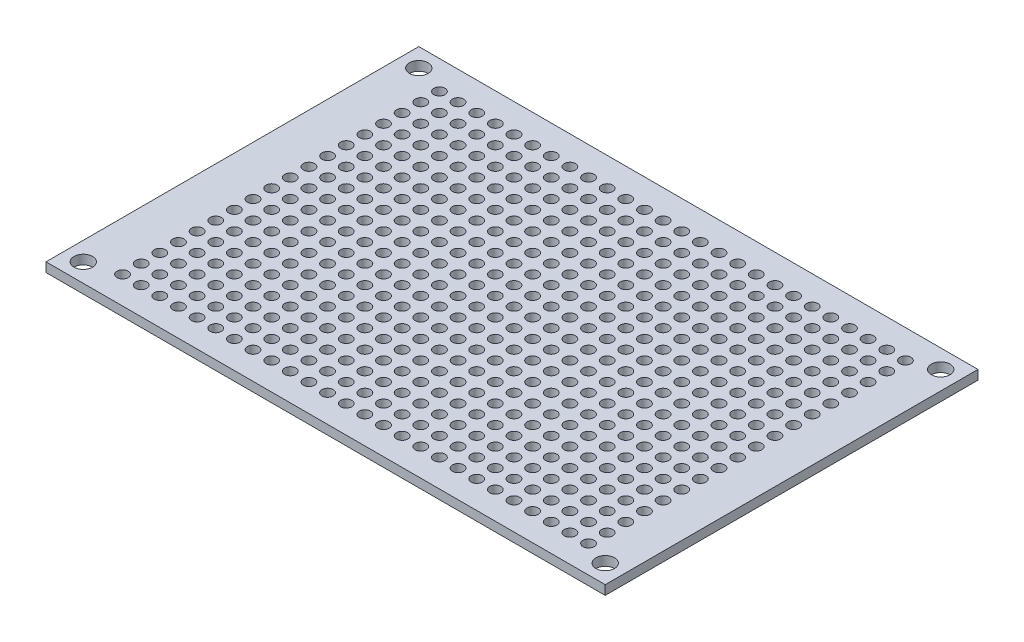
SolidWorks part; units mm, degrees
ref_plane "Front Plane" through (0, 0, 0) normal (0, 0, 1) x (1, 0, 0)
ref_plane "Top Plane" through (0, 0, 0) normal (0, 1, 0) x (1, 0, 0)
ref_plane "Right Plane" through (0, 0, 0) normal (1, 0, 0) x (0, 0, -1)
sketch "Sketch1" plane through (0, 0, 0) normal (0, 1, 0) x (1, 0, 0)
  line L1 (-30, -20) -> (30, -20)
  line L2 (-30, -20) -> (-30, 20)
  line L3 (-30, 20) -> (30, 20)
  line L4 (30, -20) -> (30, 20)
  line L5 (-30, -20) -> (30, 20) construction
  line L6 (-30, 20) -> (30, -20) construction
  circle A0 centre (-28, 18) radius 1
  circle A1 centre (28, 18) radius 1
  circle A2 centre (28, -18) radius 1
  circle A3 centre (-28, -18) radius 1
  circle A4 centre (-24.7248, 16.9363) radius 0.6
  circle A5 centre (-22.7248, 16.9363) radius 0.6
  circle A6 centre (-20.7248, 16.9363) radius 0.6
  circle A7 centre (-18.7248, 16.9363) radius 0.6
  circle A8 centre (-16.7248, 16.9363) radius 0.6
  circle A9 centre (-14.7248, 16.9363) radius 0.6
  circle A10 centre (-12.7248, 16.9363) radius 0.6
  circle A11 centre (-10.7248, 16.9363) radius 0.6
  circle A12 centre (-8.7248, 16.9363) radius 0.6
  circle A13 centre (-6.7248, 16.9363) radius 0.6
  circle A14 centre (-4.7248, 16.9363) radius 0.6
  circle A15 centre (-2.7248, 16.9363) radius 0.6
  circle A16 centre (-0.7248, 16.9363) radius 0.6
  circle A17 centre (1.2752, 16.9363) radius 0.6
  circle A18 centre (3.2752, 16.9363) radius 0.6
  circle A19 centre (5.2752, 16.9363) radius 0.6
  circle A20 centre (7.2752, 16.9363) radius 0.6
  circle A21 centre (9.2752, 16.9363) radius 0.6
  circle A22 centre (11.2752, 16.9363) radius 0.6
  circle A23 centre (13.2752, 16.9363) radius 0.6
  circle A24 centre (15.2752, 16.9363) radius 0.6
  circle A25 centre (17.2752, 16.9363) radius 0.6
  circle A26 centre (19.2752, 16.9363) radius 0.6
  circle A27 centre (21.2752, 16.9363) radius 0.6
  circle A28 centre (23.2752, 16.9363) radius 0.6
  circle A29 centre (25.2752, 16.9363) radius 0.6
  circle A30 centre (-22.7248, 14.9363) radius 0.6
  circle A31 centre (-20.7248, 14.9363) radius 0.6
  circle A32 centre (-18.7248, 14.9363) radius 0.6
  circle A33 centre (-16.7248, 14.9363) radius 0.6
  circle A34 centre (-14.7248, 14.9363) radius 0.6
  circle A35 centre (-12.7248, 14.9363) radius 0.6
  circle A36 centre (-10.7248, 14.9363) radius 0.6
  circle A37 centre (-8.7248, 14.9363) radius 0.6
  circle A38 centre (-6.7248, 14.9363) radius 0.6
  circle A39 centre (-4.7248, 14.9363) radius 0.6
  circle A40 centre (-2.7248, 14.9363) radius 0.6
  circle A41 centre (-0.7248, 14.9363) radius 0.6
  circle A42 centre (1.2752, 14.9363) radius 0.6
  circle A43 centre (3.2752, 14.9363) radius 0.6
  circle A44 centre (5.2752, 14.9363) radius 0.6
  circle A45 centre (7.2752, 14.9363) radius 0.6
  circle A46 centre (9.2752, 14.9363) radius 0.6
  circle A47 centre (11.2752, 14.9363) radius 0.6
  circle A48 centre (13.2752, 14.9363) radius 0.6
  circle A49 centre (15.2752, 14.9363) radius 0.6
  circle A50 centre (17.2752, 14.9363) radius 0.6
  circle A51 centre (19.2752, 14.9363) radius 0.6
  circle A52 centre (21.2752, 14.9363) radius 0.6
  circle A53 centre (23.2752, 14.9363) radius 0.6
  circle A54 centre (25.2752, 14.9363) radius 0.6
  circle A55 centre (-22.7248, 12.9363) radius 0.6
  circle A56 centre (-20.7248, 12.9363) radius 0.6
  circle A57 centre (-18.7248, 12.9363) radius 0.6
  circle A58 centre (-16.7248, 12.9363) radius 0.6
  circle A59 centre (-14.7248, 12.9363) radius 0.6
  circle A60 centre (-12.7248, 12.9363) radius 0.6
  circle A61 centre (-10.7248, 12.9363) radius 0.6
  circle A62 centre (-8.7248, 12.9363) radius 0.6
  circle A63 centre (-6.7248, 12.9363) radius 0.6
  circle A64 centre (-4.7248, 12.9363) radius 0.6
  circle A65 centre (-2.7248, 12.9363) radius 0.6
  circle A66 centre (-0.7248, 12.9363) radius 0.6
  circle A67 centre (1.2752, 12.9363) radius 0.6
  circle A68 centre (3.2752, 12.9363) radius 0.6
  circle A69 centre (5.2752, 12.9363) radius 0.6
  circle A70 centre (7.2752, 12.9363) radius 0.6
  circle A71 centre (9.2752, 12.9363) radius 0.6
  circle A72 centre (11.2752, 12.9363) radius 0.6
  circle A73 centre (13.2752, 12.9363) radius 0.6
  circle A74 centre (15.2752, 12.9363) radius 0.6
  circle A75 centre (17.2752, 12.9363) radius 0.6
  circle A76 centre (19.2752, 12.9363) radius 0.6
  circle A77 centre (21.2752, 12.9363) radius 0.6
  circle A78 centre (23.2752, 12.9363) radius 0.6
  circle A79 centre (25.2752, 12.9363) radius 0.6
  circle A80 centre (-22.7248, 10.9363) radius 0.6
  circle A81 centre (-20.7248, 10.9363) radius 0.6
  circle A82 centre (-18.7248, 10.9363) radius 0.6
  circle A83 centre (-16.7248, 10.9363) radius 0.6
  circle A84 centre (-14.7248, 10.9363) radius 0.6
  circle A85 centre (-12.7248, 10.9363) radius 0.6
  circle A86 centre (-10.7248, 10.9363) radius 0.6
  circle A87 centre (-8.7248, 10.9363) radius 0.6
  circle A88 centre (-6.7248, 10.9363) radius 0.6
  circle A89 centre (-4.7248, 10.9363) radius 0.6
  circle A90 centre (-2.7248, 10.9363) radius 0.6
  circle A91 centre (-0.7248, 10.9363) radius 0.6
  circle A92 centre (1.2752, 10.9363) radius 0.6
  circle A93 centre (3.2752, 10.9363) radius 0.6
  circle A94 centre (5.2752, 10.9363) radius 0.6
  circle A95 centre (7.2752, 10.9363) radius 0.6
  circle A96 centre (9.2752, 10.9363) radius 0.6
  circle A97 centre (11.2752, 10.9363) radius 0.6
  circle A98 centre (13.2752, 10.9363) radius 0.6
  circle A99 centre (15.2752, 10.9363) radius 0.6
  circle A100 centre (17.2752, 10.9363) radius 0.6
  circle A101 centre (19.2752, 10.9363) radius 0.6
  circle A102 centre (21.2752, 10.9363) radius 0.6
  circle A103 centre (23.2752, 10.9363) radius 0.6
  circle A104 centre (25.2752, 10.9363) radius 0.6
  circle A105 centre (-22.7248, 8.9363) radius 0.6
  circle A106 centre (-20.7248, 8.9363) radius 0.6
  circle A107 centre (-18.7248, 8.9363) radius 0.6
  circle A108 centre (-16.7248, 8.9363) radius 0.6
  circle A109 centre (-14.7248, 8.9363) radius 0.6
  circle A110 centre (-12.7248, 8.9363) radius 0.6
  circle A111 centre (-10.7248, 8.9363) radius 0.6
  circle A112 centre (-8.7248, 8.9363) radius 0.6
  circle A113 centre (-6.7248, 8.9363) radius 0.6
  circle A114 centre (-4.7248, 8.9363) radius 0.6
  circle A115 centre (-2.7248, 8.9363) radius 0.6
  circle A116 centre (-0.7248, 8.9363) radius 0.6
  circle A117 centre (1.2752, 8.9363) radius 0.6
  circle A118 centre (3.2752, 8.9363) radius 0.6
  circle A119 centre (5.2752, 8.9363) radius 0.6
  circle A120 centre (7.2752, 8.9363) radius 0.6
  circle A121 centre (9.2752, 8.9363) radius 0.6
  circle A122 centre (11.2752, 8.9363) radius 0.6
  circle A123 centre (13.2752, 8.9363) radius 0.6
  circle A124 centre (15.2752, 8.9363) radius 0.6
  circle A125 centre (17.2752, 8.9363) radius 0.6
  circle A126 centre (19.2752, 8.9363) radius 0.6
  circle A127 centre (21.2752, 8.9363) radius 0.6
  circle A128 centre (23.2752, 8.9363) radius 0.6
  circle A129 centre (25.2752, 8.9363) radius 0.6
  circle A130 centre (-22.7248, 6.9363) radius 0.6
  circle A131 centre (-20.7248, 6.9363) radius 0.6
  circle A132 centre (-18.7248, 6.9363) radius 0.6
  circle A133 centre (-16.7248, 6.9363) radius 0.6
  circle A134 centre (-14.7248, 6.9363) radius 0.6
  circle A135 centre (-12.7248, 6.9363) radius 0.6
  circle A136 centre (-10.7248, 6.9363) radius 0.6
  circle A137 centre (-8.7248, 6.9363) radius 0.6
  circle A138 centre (-6.7248, 6.9363) radius 0.6
  circle A139 centre (-4.7248, 6.9363) radius 0.6
  circle A140 centre (-2.7248, 6.9363) radius 0.6
  circle A141 centre (-0.7248, 6.9363) radius 0.6
  circle A142 centre (1.2752, 6.9363) radius 0.6
  circle A143 centre (3.2752, 6.9363) radius 0.6
  circle A144 centre (5.2752, 6.9363) radius 0.6
  circle A145 centre (7.2752, 6.9363) radius 0.6
  circle A146 centre (9.2752, 6.9363) radius 0.6
  circle A147 centre (11.2752, 6.9363) radius 0.6
  circle A148 centre (13.2752, 6.9363) radius 0.6
  circle A149 centre (15.2752, 6.9363) radius 0.6
  circle A150 centre (17.2752, 6.9363) radius 0.6
  circle A151 centre (19.2752, 6.9363) radius 0.6
  circle A152 centre (21.2752, 6.9363) radius 0.6
  circle A153 centre (23.2752, 6.9363) radius 0.6
  circle A154 centre (25.2752, 6.9363) radius 0.6
  circle A155 centre (-22.7248, 4.9363) radius 0.6
  circle A156 centre (-20.7248, 4.9363) radius 0.6
  circle A157 centre (-18.7248, 4.9363) radius 0.6
  circle A158 centre (-16.7248, 4.9363) radius 0.6
  circle A159 centre (-14.7248, 4.9363) radius 0.6
  circle A160 centre (-12.7248, 4.9363) radius 0.6
  circle A161 centre (-10.7248, 4.9363) radius 0.6
  circle A162 centre (-8.7248, 4.9363) radius 0.6
  circle A163 centre (-6.7248, 4.9363) radius 0.6
  circle A164 centre (-4.7248, 4.9363) radius 0.6
  circle A165 centre (-2.7248, 4.9363) radius 0.6
  circle A166 centre (-0.7248, 4.9363) radius 0.6
  circle A167 centre (1.2752, 4.9363) radius 0.6
  circle A168 centre (3.2752, 4.9363) radius 0.6
  circle A169 centre (5.2752, 4.9363) radius 0.6
  circle A170 centre (7.2752, 4.9363) radius 0.6
  circle A171 centre (9.2752, 4.9363) radius 0.6
  circle A172 centre (11.2752, 4.9363) radius 0.6
  circle A173 centre (13.2752, 4.9363) radius 0.6
  circle A174 centre (15.2752, 4.9363) radius 0.6
  circle A175 centre (17.2752, 4.9363) radius 0.6
  circle A176 centre (19.2752, 4.9363) radius 0.6
  circle A177 centre (21.2752, 4.9363) radius 0.6
  circle A178 centre (23.2752, 4.9363) radius 0.6
  circle A179 centre (25.2752, 4.9363) radius 0.6
  circle A180 centre (-22.7248, 2.9363) radius 0.6
  circle A181 centre (-20.7248, 2.9363) radius 0.6
  circle A182 centre (-18.7248, 2.9363) radius 0.6
  circle A183 centre (-16.7248, 2.9363) radius 0.6
  circle A184 centre (-14.7248, 2.9363) radius 0.6
  circle A185 centre (-12.7248, 2.9363) radius 0.6
  circle A186 centre (-10.7248, 2.9363) radius 0.6
  circle A187 centre (-8.7248, 2.9363) radius 0.6
  circle A188 centre (-6.7248, 2.9363) radius 0.6
  circle A189 centre (-4.7248, 2.9363) radius 0.6
  circle A190 centre (-2.7248, 2.9363) radius 0.6
  circle A191 centre (-0.7248, 2.9363) radius 0.6
  circle A192 centre (1.2752, 2.9363) radius 0.6
  circle A193 centre (3.2752, 2.9363) radius 0.6
  circle A194 centre (5.2752, 2.9363) radius 0.6
  circle A195 centre (7.2752, 2.9363) radius 0.6
  circle A196 centre (9.2752, 2.9363) radius 0.6
  circle A197 centre (11.2752, 2.9363) radius 0.6
  circle A198 centre (13.2752, 2.9363) radius 0.6
  circle A199 centre (15.2752, 2.9363) radius 0.6
  circle A200 centre (17.2752, 2.9363) radius 0.6
  circle A201 centre (19.2752, 2.9363) radius 0.6
  circle A202 centre (21.2752, 2.9363) radius 0.6
  circle A203 centre (23.2752, 2.9363) radius 0.6
  circle A204 centre (25.2752, 2.9363) radius 0.6
  circle A205 centre (-22.7248, 0.9363) radius 0.6
  circle A206 centre (-20.7248, 0.9363) radius 0.6
  circle A207 centre (-18.7248, 0.9363) radius 0.6
  circle A208 centre (-16.7248, 0.9363) radius 0.6
  circle A209 centre (-14.7248, 0.9363) radius 0.6
  circle A210 centre (-12.7248, 0.9363) radius 0.6
  circle A211 centre (-10.7248, 0.9363) radius 0.6
  circle A212 centre (-8.7248, 0.9363) radius 0.6
  circle A213 centre (-6.7248, 0.9363) radius 0.6
  circle A214 centre (-4.7248, 0.9363) radius 0.6
  circle A215 centre (-2.7248, 0.9363) radius 0.6
  circle A216 centre (-0.7248, 0.9363) radius 0.6
  circle A217 centre (1.2752, 0.9363) radius 0.6
  circle A218 centre (3.2752, 0.9363) radius 0.6
  circle A219 centre (5.2752, 0.9363) radius 0.6
  circle A220 centre (7.2752, 0.9363) radius 0.6
  circle A221 centre (9.2752, 0.9363) radius 0.6
  circle A222 centre (11.2752, 0.9363) radius 0.6
  circle A223 centre (13.2752, 0.9363) radius 0.6
  circle A224 centre (15.2752, 0.9363) radius 0.6
  circle A225 centre (17.2752, 0.9363) radius 0.6
  circle A226 centre (19.2752, 0.9363) radius 0.6
  circle A227 centre (21.2752, 0.9363) radius 0.6
  circle A228 centre (23.2752, 0.9363) radius 0.6
  circle A229 centre (25.2752, 0.9363) radius 0.6
  circle A230 centre (-22.7248, -1.0637) radius 0.6
  circle A231 centre (-20.7248, -1.0637) radius 0.6
  circle A232 centre (-18.7248, -1.0637) radius 0.6
  circle A233 centre (-16.7248, -1.0637) radius 0.6
  circle A234 centre (-14.7248, -1.0637) radius 0.6
  circle A235 centre (-12.7248, -1.0637) radius 0.6
  circle A236 centre (-10.7248, -1.0637) radius 0.6
  circle A237 centre (-8.7248, -1.0637) radius 0.6
  circle A238 centre (-6.7248, -1.0637) radius 0.6
  circle A239 centre (-4.7248, -1.0637) radius 0.6
  circle A240 centre (-2.7248, -1.0637) radius 0.6
  circle A241 centre (-0.7248, -1.0637) radius 0.6
  circle A242 centre (1.2752, -1.0637) radius 0.6
  circle A243 centre (3.2752, -1.0637) radius 0.6
  circle A244 centre (5.2752, -1.0637) radius 0.6
  circle A245 centre (7.2752, -1.0637) radius 0.6
  circle A246 centre (9.2752, -1.0637) radius 0.6
  circle A247 centre (11.2752, -1.0637) radius 0.6
  circle A248 centre (13.2752, -1.0637) radius 0.6
  circle A249 centre (15.2752, -1.0637) radius 0.6
  circle A250 centre (17.2752, -1.0637) radius 0.6
  circle A251 centre (19.2752, -1.0637) radius 0.6
  circle A252 centre (21.2752, -1.0637) radius 0.6
  circle A253 centre (23.2752, -1.0637) radius 0.6
  circle A254 centre (25.2752, -1.0637) radius 0.6
  circle A255 centre (-22.7248, -3.0637) radius 0.6
  circle A256 centre (-20.7248, -3.0637) radius 0.6
  circle A257 centre (-18.7248, -3.0637) radius 0.6
  circle A258 centre (-16.7248, -3.0637) radius 0.6
  circle A259 centre (-14.7248, -3.0637) radius 0.6
  circle A260 centre (-12.7248, -3.0637) radius 0.6
  circle A261 centre (-10.7248, -3.0637) radius 0.6
  circle A262 centre (-8.7248, -3.0637) radius 0.6
  circle A263 centre (-6.7248, -3.0637) radius 0.6
  circle A264 centre (-4.7248, -3.0637) radius 0.6
  circle A265 centre (-2.7248, -3.0637) radius 0.6
  circle A266 centre (-0.7248, -3.0637) radius 0.6
  circle A267 centre (1.2752, -3.0637) radius 0.6
  circle A268 centre (3.2752, -3.0637) radius 0.6
  circle A269 centre (5.2752, -3.0637) radius 0.6
  circle A270 centre (7.2752, -3.0637) radius 0.6
  circle A271 centre (9.2752, -3.0637) radius 0.6
  circle A272 centre (11.2752, -3.0637) radius 0.6
  circle A273 centre (13.2752, -3.0637) radius 0.6
  circle A274 centre (15.2752, -3.0637) radius 0.6
  circle A275 centre (17.2752, -3.0637) radius 0.6
  circle A276 centre (19.2752, -3.0637) radius 0.6
  circle A277 centre (21.2752, -3.0637) radius 0.6
  circle A278 centre (23.2752, -3.0637) radius 0.6
  circle A279 centre (25.2752, -3.0637) radius 0.6
  circle A280 centre (-22.7248, -5.0637) radius 0.6
  circle A281 centre (-20.7248, -5.0637) radius 0.6
  circle A282 centre (-18.7248, -5.0637) radius 0.6
  circle A283 centre (-16.7248, -5.0637) radius 0.6
  circle A284 centre (-14.7248, -5.0637) radius 0.6
  circle A285 centre (-12.7248, -5.0637) radius 0.6
  circle A286 centre (-10.7248, -5.0637) radius 0.6
  circle A287 centre (-8.7248, -5.0637) radius 0.6
  circle A288 centre (-6.7248, -5.0637) radius 0.6
  circle A289 centre (-4.7248, -5.0637) radius 0.6
  circle A290 centre (-2.7248, -5.0637) radius 0.6
  circle A291 centre (-0.7248, -5.0637) radius 0.6
  circle A292 centre (1.2752, -5.0637) radius 0.6
  circle A293 centre (3.2752, -5.0637) radius 0.6
  circle A294 centre (5.2752, -5.0637) radius 0.6
  circle A295 centre (7.2752, -5.0637) radius 0.6
  circle A296 centre (9.2752, -5.0637) radius 0.6
  circle A297 centre (11.2752, -5.0637) radius 0.6
  circle A298 centre (13.2752, -5.0637) radius 0.6
  circle A299 centre (15.2752, -5.0637) radius 0.6
  circle A300 centre (17.2752, -5.0637) radius 0.6
  circle A301 centre (19.2752, -5.0637) radius 0.6
  circle A302 centre (21.2752, -5.0637) radius 0.6
  circle A303 centre (23.2752, -5.0637) radius 0.6
  circle A304 centre (25.2752, -5.0637) radius 0.6
  circle A305 centre (-22.7248, -7.0637) radius 0.6
  circle A306 centre (-20.7248, -7.0637) radius 0.6
  circle A307 centre (-18.7248, -7.0637) radius 0.6
  circle A308 centre (-16.7248, -7.0637) radius 0.6
  circle A309 centre (-14.7248, -7.0637) radius 0.6
  circle A310 centre (-12.7248, -7.0637) radius 0.6
  circle A311 centre (-10.7248, -7.0637) radius 0.6
  circle A312 centre (-8.7248, -7.0637) radius 0.6
  circle A313 centre (-6.7248, -7.0637) radius 0.6
  circle A314 centre (-4.7248, -7.0637) radius 0.6
  circle A315 centre (-2.7248, -7.0637) radius 0.6
  circle A316 centre (-0.7248, -7.0637) radius 0.6
  circle A317 centre (1.2752, -7.0637) radius 0.6
  circle A318 centre (3.2752, -7.0637) radius 0.6
  circle A319 centre (5.2752, -7.0637) radius 0.6
  circle A320 centre (7.2752, -7.0637) radius 0.6
  circle A321 centre (9.2752, -7.0637) radius 0.6
  circle A322 centre (11.2752, -7.0637) radius 0.6
  circle A323 centre (13.2752, -7.0637) radius 0.6
  circle A324 centre (15.2752, -7.0637) radius 0.6
  circle A325 centre (17.2752, -7.0637) radius 0.6
  circle A326 centre (19.2752, -7.0637) radius 0.6
  circle A327 centre (21.2752, -7.0637) radius 0.6
  circle A328 centre (23.2752, -7.0637) radius 0.6
  circle A329 centre (25.2752, -7.0637) radius 0.6
  circle A330 centre (-22.7248, -9.0637) radius 0.6
  circle A331 centre (-20.7248, -9.0637) radius 0.6
  circle A332 centre (-18.7248, -9.0637) radius 0.6
  circle A333 centre (-16.7248, -9.0637) radius 0.6
  circle A334 centre (-14.7248, -9.0637) radius 0.6
  circle A335 centre (-12.7248, -9.0637) radius 0.6
  circle A336 centre (-10.7248, -9.0637) radius 0.6
  circle A337 centre (-8.7248, -9.0637) radius 0.6
  circle A338 centre (-6.7248, -9.0637) radius 0.6
  circle A339 centre (-4.7248, -9.0637) radius 0.6
  circle A340 centre (-2.7248, -9.0637) radius 0.6
  circle A341 centre (-0.7248, -9.0637) radius 0.6
  circle A342 centre (1.2752, -9.0637) radius 0.6
  circle A343 centre (3.2752, -9.0637) radius 0.6
  circle A344 centre (5.2752, -9.0637) radius 0.6
  circle A345 centre (7.2752, -9.0637) radius 0.6
  circle A346 centre (9.2752, -9.0637) radius 0.6
  circle A347 centre (11.2752, -9.0637) radius 0.6
  circle A348 centre (13.2752, -9.0637) radius 0.6
  circle A349 centre (15.2752, -9.0637) radius 0.6
  circle A350 centre (17.2752, -9.0637) radius 0.6
  circle A351 centre (19.2752, -9.0637) radius 0.6
  circle A352 centre (21.2752, -9.0637) radius 0.6
  circle A353 centre (23.2752, -9.0637) radius 0.6
  circle A354 centre (25.2752, -9.0637) radius 0.6
  circle A355 centre (-22.7248, -11.0637) radius 0.6
  circle A356 centre (-20.7248, -11.0637) radius 0.6
  circle A357 centre (-18.7248, -11.0637) radius 0.6
  circle A358 centre (-16.7248, -11.0637) radius 0.6
  circle A359 centre (-14.7248, -11.0637) radius 0.6
  circle A360 centre (-12.7248, -11.0637) radius 0.6
  circle A361 centre (-10.7248, -11.0637) radius 0.6
  circle A362 centre (-8.7248, -11.0637) radius 0.6
  circle A363 centre (-6.7248, -11.0637) radius 0.6
  circle A364 centre (-4.7248, -11.0637) radius 0.6
  circle A365 centre (-2.7248, -11.0637) radius 0.6
  circle A366 centre (-0.7248, -11.0637) radius 0.6
  circle A367 centre (1.2752, -11.0637) radius 0.6
  circle A368 centre (3.2752, -11.0637) radius 0.6
  circle A369 centre (5.2752, -11.0637) radius 0.6
  circle A370 centre (7.2752, -11.0637) radius 0.6
  circle A371 centre (9.2752, -11.0637) radius 0.6
  circle A372 centre (11.2752, -11.0637) radius 0.6
  circle A373 centre (13.2752, -11.0637) radius 0.6
  circle A374 centre (15.2752, -11.0637) radius 0.6
  circle A375 centre (17.2752, -11.0637) radius 0.6
  circle A376 centre (19.2752, -11.0637) radius 0.6
  circle A377 centre (21.2752, -11.0637) radius 0.6
  circle A378 centre (23.2752, -11.0637) radius 0.6
  circle A379 centre (25.2752, -11.0637) radius 0.6
  circle A380 centre (-22.7248, -13.0637) radius 0.6
  circle A381 centre (-20.7248, -13.0637) radius 0.6
  circle A382 centre (-18.7248, -13.0637) radius 0.6
  circle A383 centre (-16.7248, -13.0637) radius 0.6
  circle A384 centre (-14.7248, -13.0637) radius 0.6
  circle A385 centre (-12.7248, -13.0637) radius 0.6
  circle A386 centre (-10.7248, -13.0637) radius 0.6
  circle A387 centre (-8.7248, -13.0637) radius 0.6
  circle A388 centre (-6.7248, -13.0637) radius 0.6
  circle A389 centre (-4.7248, -13.0637) radius 0.6
  circle A390 centre (-2.7248, -13.0637) radius 0.6
  circle A391 centre (-0.7248, -13.0637) radius 0.6
  circle A392 centre (1.2752, -13.0637) radius 0.6
  circle A393 centre (3.2752, -13.0637) radius 0.6
  circle A394 centre (5.2752, -13.0637) radius 0.6
  circle A395 centre (7.2752, -13.0637) radius 0.6
  circle A396 centre (9.2752, -13.0637) radius 0.6
  circle A397 centre (11.2752, -13.0637) radius 0.6
  circle A398 centre (13.2752, -13.0637) radius 0.6
  circle A399 centre (15.2752, -13.0637) radius 0.6
  circle A400 centre (17.2752, -13.0637) radius 0.6
  circle A401 centre (19.2752, -13.0637) radius 0.6
  circle A402 centre (21.2752, -13.0637) radius 0.6
  circle A403 centre (23.2752, -13.0637) radius 0.6
  circle A404 centre (25.2752, -13.0637) radius 0.6
  circle A405 centre (-22.7248, -15.0637) radius 0.6
  circle A406 centre (-20.7248, -15.0637) radius 0.6
  circle A407 centre (-18.7248, -15.0637) radius 0.6
  circle A408 centre (-16.7248, -15.0637) radius 0.6
  circle A409 centre (-14.7248, -15.0637) radius 0.6
  circle A410 centre (-12.7248, -15.0637) radius 0.6
  circle A411 centre (-10.7248, -15.0637) radius 0.6
  circle A412 centre (-8.7248, -15.0637) radius 0.6
  circle A413 centre (-6.7248, -15.0637) radius 0.6
  circle A414 centre (-4.7248, -15.0637) radius 0.6
  circle A415 centre (-2.7248, -15.0637) radius 0.6
  circle A416 centre (-0.7248, -15.0637) radius 0.6
  circle A417 centre (1.2752, -15.0637) radius 0.6
  circle A418 centre (3.2752, -15.0637) radius 0.6
  circle A419 centre (5.2752, -15.0637) radius 0.6
  circle A420 centre (7.2752, -15.0637) radius 0.6
  circle A421 centre (9.2752, -15.0637) radius 0.6
  circle A422 centre (11.2752, -15.0637) radius 0.6
  circle A423 centre (13.2752, -15.0637) radius 0.6
  circle A424 centre (15.2752, -15.0637) radius 0.6
  circle A425 centre (17.2752, -15.0637) radius 0.6
  circle A426 centre (19.2752, -15.0637) radius 0.6
  circle A427 centre (21.2752, -15.0637) radius 0.6
  circle A428 centre (23.2752, -15.0637) radius 0.6
  circle A429 centre (25.2752, -15.0637) radius 0.6
  circle A430 centre (-22.7248, -17.0637) radius 0.6
  circle A431 centre (-20.7248, -17.0637) radius 0.6
  circle A432 centre (-18.7248, -17.0637) radius 0.6
  circle A433 centre (-16.7248, -17.0637) radius 0.6
  circle A434 centre (-14.7248, -17.0637) radius 0.6
  circle A435 centre (-12.7248, -17.0637) radius 0.6
  circle A436 centre (-10.7248, -17.0637) radius 0.6
  circle A437 centre (-8.7248, -17.0637) radius 0.6
  circle A438 centre (-6.7248, -17.0637) radius 0.6
  circle A439 centre (-4.7248, -17.0637) radius 0.6
  circle A440 centre (-2.7248, -17.0637) radius 0.6
  circle A441 centre (-0.7248, -17.0637) radius 0.6
  circle A442 centre (1.2752, -17.0637) radius 0.6
  circle A443 centre (3.2752, -17.0637) radius 0.6
  circle A444 centre (5.2752, -17.0637) radius 0.6
  circle A445 centre (7.2752, -17.0637) radius 0.6
  circle A446 centre (9.2752, -17.0637) radius 0.6
  circle A447 centre (11.2752, -17.0637) radius 0.6
  circle A448 centre (13.2752, -17.0637) radius 0.6
  circle A449 centre (15.2752, -17.0637) radius 0.6
  circle A450 centre (17.2752, -17.0637) radius 0.6
  circle A451 centre (19.2752, -17.0637) radius 0.6
  circle A452 centre (21.2752, -17.0637) radius 0.6
  circle A453 centre (23.2752, -17.0637) radius 0.6
  circle A454 centre (25.2752, -17.0637) radius 0.6
  circle A455 centre (-24.7248, 14.9363) radius 0.6
  circle A456 centre (-24.7248, 12.9363) radius 0.6
  circle A457 centre (-24.7248, 10.9363) radius 0.6
  circle A458 centre (-24.7248, 8.9363) radius 0.6
  circle A459 centre (-24.7248, 6.9363) radius 0.6
  circle A460 centre (-24.7248, 4.9363) radius 0.6
  circle A461 centre (-24.7248, 2.9363) radius 0.6
  circle A462 centre (-24.7248, 0.9363) radius 0.6
  circle A463 centre (-24.7248, -1.0637) radius 0.6
  circle A464 centre (-24.7248, -3.0637) radius 0.6
  circle A465 centre (-24.7248, -5.0637) radius 0.6
  circle A466 centre (-24.7248, -7.0637) radius 0.6
  circle A467 centre (-24.7248, -9.0637) radius 0.6
  circle A468 centre (-24.7248, -11.0637) radius 0.6
  circle A469 centre (-24.7248, -13.0637) radius 0.6
  circle A470 centre (-24.7248, -15.0637) radius 0.6
  circle A471 centre (-24.7248, -17.0637) radius 0.6
  point P0 (0, 0)
  dimension "D3" = 2
  dimension "D4" = 2
  dimension "D5" = 2
  dimension "D6" = 2
  dimension "D7" = 2
  dimension "D8" = 1.2
  dimension "D1" = 60
  dimension "D2" = 40
  dimension "D9" = 26
  dimension "D10" = 18
extrude "Boss-Extrude1" add sketch "Sketch1" along normal blind 1
